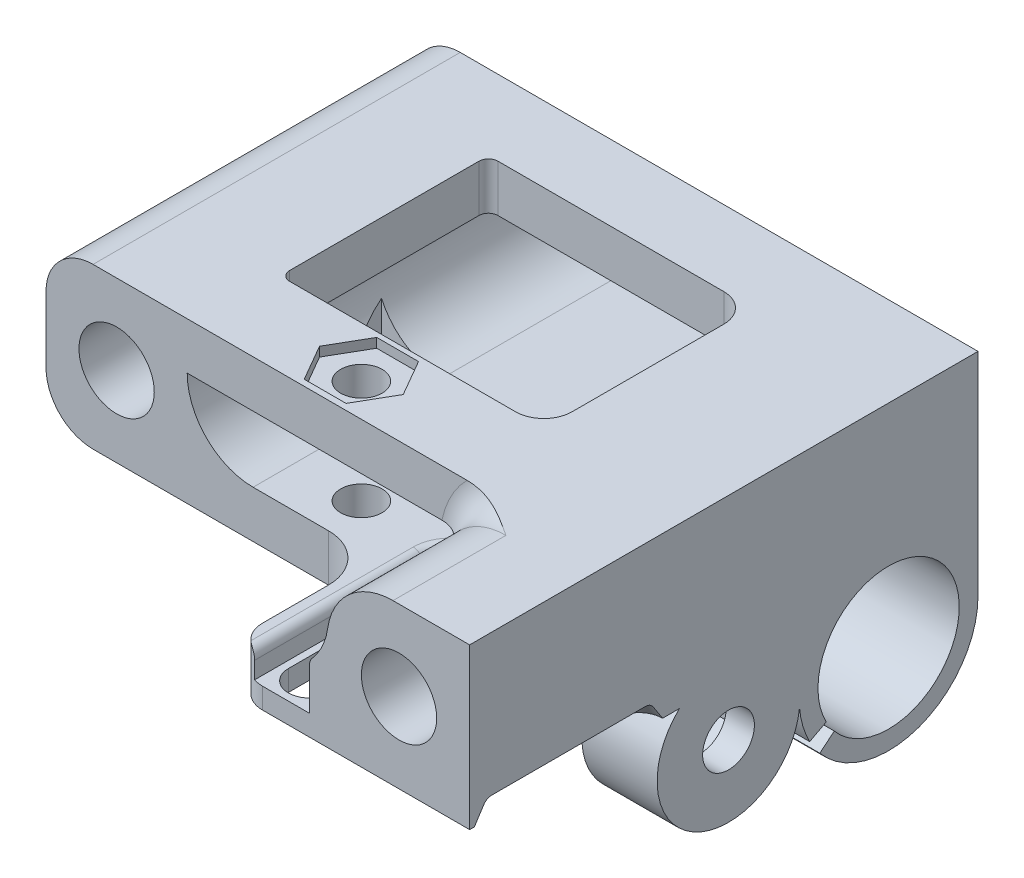
SolidWorks part; units mm, degrees
material "ABS generico"
ref_plane "Front Plane" through (0, 0, 0) normal (0, 0, 1) x (1, 0, 0)
ref_plane "Top Plane" through (0, 0, 0) normal (0, 1, 0) x (1, 0, 0)
ref_plane "Right Plane" through (0, 0, 0) normal (1, 0, 0) x (0, 0, -1)
sketch "Sketch1" plane through (0, 0, 0) normal (1, 0, 0) x (0, 0, -1)
  line L1 (21.1236, -26.9641) -> (22.8813, -26.0274)
  line L3 (23.7305, -27.2923) -> (22.1984, -28.5649)
  line L4 (20.0416, -23.294) -> (20.0416, -17)
  line L8 (39, 0) -> (0, 0)
  line L12 (0, -17) -> (0, 0)
  line L13 (0, -17) -> (20.0416, -17)
  line L15 (39, -22.5) -> (39, 0)
  line L19 (16.5, -29.4282) -> (20.0416, -23.294) construction
  line L20 (8.5, -29.4282) -> (16.5, -29.4282) construction
  line L21 (4.5, -22.5) -> (8.5, -29.4282) construction
  line L22 (4.5, -17) -> (4.5, -22.5) construction
  arc A0 (23.7305, -27.2923) -> (22.8813, -26.0274) centre (29.5041, -22.4988) ccw
  arc A1 (20.0416, -23.294) -> (21.1236, -26.9641) centre (29.5041, -22.4988) ccw
  arc A2 (22.1984, -28.5649) -> (39, -22.5) centre (29.5041, -22.4988) ccw
  circle A5 centre (12.5, -22.5) radius 2.75 construction
  dimension "D2" = 7.5042
  dimension "D3" = 9.4959
  dimension "D1" = 39
  dimension "D4" = 17
extrude "Extrude1" add sketch "Sketch1" against normal blind 60
sketch "Sketch2" plane through (0, 0, 0) normal (0, 0, 1) x (1, 0, 0)
  line L0 (-60, -8.5) -> (0, -8.5) construction
  line L1 (-60, 0) -> (-60, -17) construction
  line L2 (0, 0) -> (0, -17) construction
  line L3 (-30, 1.8171) -> (-30, -40.9837) construction
  line L5 (-15, -12) -> (-45, -12)
  line L6 (-15, -12) -> (-15, -5)
  line L7 (-15, -5) -> (-45, -5)
  line L8 (-45, -12) -> (-45, -5)
  line L9 (-15, -12) -> (-45, -5) construction
  line L10 (-15, -5) -> (-45, -12) construction
  circle A0 centre (-52.5, -8.5) radius 4
  circle A1 centre (-7.5, -8.5) radius 4
  point P12 (-30, -8.5)
  dimension "D1" = 8
  dimension "D2" = 22.5
  dimension "D3" = 7.5
  dimension "D4" = 7
  dimension "D5" = 30
extrude "Extrude2" cut sketch "Sketch2" against normal up to surface (39 mm away) up to face at (-30, -11.25, -39)
sketch "Sketch3" plane through (0, 0, 0) normal (0, 0, 1) x (1, 0, 0)
  line L0 (-52.5, -8.5) -> (-7.5, -8.5) construction
  line L1 (-52.5, -8.5) -> (-52.5, 8.8734) construction
  line L2 (-32.5, -8.5) -> (-32.5, 8.8734) construction
  dimension "D1" = 20
sketch "Sketch4" plane through (0, 0, 0) normal (1, 0, 0) x (0, 0, -1)
  line L0 (7.2804, -17) -> (20.0416, -17)
  line L1 (12.5, -17.9967) -> (8.6, -20.2483) construction
  line L2 (8.6, -20.2483) -> (8.6, -24.7517) construction
  line L3 (8.6, -24.7517) -> (12.5, -27.0033) construction
  line L4 (12.5, -27.0033) -> (16.4, -24.7517) construction
  line L5 (16.4, -24.7517) -> (16.4, -20.2483) construction
  line L6 (16.4, -20.2483) -> (12.5, -17.9967) construction
  line L7 (0, -17) -> (20.0416, -17) construction
  line L8 (20.0416, -17) -> (20.0817, -22.3872)
  circle A0 centre (12.5, -22.5) radius 3.9 construction
  arc A1 (7.2804, -17) -> (20.0817, -22.3872) centre (12.5, -22.5) ccw
  dimension "D1" = 7.8
extrude "Extrude3" add sketch "Sketch4" against normal blind 8
sketch "Sketch5" plane through (0, 0, 0) normal (1, 0, 0) x (0, 0, -1)
  circle A0 centre (12.5, -22.5) radius 2.75
  dimension "D1" = 5.5
extrude "Extrude4" cut sketch "Sketch5" against normal up to surface (8 mm away) up to face at (-8, -22.1484, -14.2839)
sketch "Sketch6" plane through (-8, 0, 0) normal (-1, 0, 0) x (0, 0, 1)
  line L1 (-12.5, -17.8812) -> (-16.5, -20.1906)
  line L2 (-16.5, -20.1906) -> (-16.5, -24.8094)
  line L3 (-16.5, -24.8094) -> (-12.5, -27.1188)
  line L4 (-12.5, -27.1188) -> (-8.5, -24.8094)
  line L5 (-8.5, -24.8094) -> (-8.5, -20.1906)
  line L6 (-8.5, -20.1906) -> (-12.5, -17.8812)
extrude "Extrude5" cut sketch "Sketch6" against normal blind 5
sketch "Sketch7" plane through (0, 0, 0) normal (0, 1, 0) x (1, 0, 0)
  line L2 (-31, -370.8295) -> (-31, 97.9462) construction
  line L6 (-30.9897, -180.6724) -> (-30.9897, -405.4164) construction
  circle A0 centre (-31, 4.5) radius 2.2
extrude "Extrude6" cut sketch "Sketch7" against normal up to surface (17 mm away) up to face at (-22.6667, -17, -9.1073)
sketch "Sketch8" plane through (0, 0, -39) normal (0, 0, -1) x (-1, 0, 0)
  line L0 (7.5, -8.5) -> (52.5, -8.5) construction
  line L1 (30, -8.5) -> (30, 3.0319) construction
  circle A0 centre (7.5, -8.5) radius 4.201
  circle A1 centre (52.5, -8.5) radius 1.25
  circle A2 centre (7.5, -8.5) radius 1.25
  circle A3 centre (52.5, -8.5) radius 4.201
  dimension "D1" = 2.5
extrude "Extrude7" add sketch "Sketch8" against normal blind 5
sketch "Sketch10" plane through (-60, 0, 0) normal (-1, 0, 0) x (0, 0, 1)
  line L1 (-20.0416, -17) -> (-39.247, -17)
  line L2 (-20.0416, -17) -> (-20.0416, -32.1139)
  line L3 (-20.0416, -32.1139) -> (-39.247, -32.1139)
  line L4 (-39.247, -17) -> (-39.247, -32.1139)
extrude "Extrude8" cut sketch "Sketch10" against normal blind 10
fillet "Fillet9" radius 10 2 edges at (-55, -17, -24.3976) (-55, -17, -34.6107)
fillet "Fillet11" radius 5 1 edges at (-60, 0, -19.5)
fillet "Fillet12" radius 5 5 edges at (-60, -17, -38.3198) (-60, -16.7094, -35.2462) (-60, -14.9946, -29.5041) (-60, -16.7094, -23.7621) (-60, -17, -10.6843)
sketch "Sketch12" plane through (0, 0, 0) normal (0, 0, 1) x (1, 0, 0)
  line L0 (-15, -12) -> (-15, 2.5343) construction
  line L1 (0, 0) -> (-20.7492, 0) construction
  line L2 (-55, 0) -> (0, 0) construction
  line L3 (-45, -12) -> (-15, -12) construction
  line L4 (-15, 0) -> (0, 0)
  line L5 (-11.5, -8.5) -> (-11.5, 2.5343) construction
  line L6 (-15, -17) -> (0, -17)
  line L7 (0, 0) -> (0, -17)
  line L8 (-15, -17) -> (-25, -17)
  line L9 (-25, -12) -> (-15, -12)
  line L10 (-15, -12) -> (-15, 0)
  line L11 (-25, -17) -> (-25, -12)
  circle A0 centre (-7.5, -8.5) radius 4
  point P21 (-14.5, -8.5)
  point P22 (-14.5, 2.5343)
  dimension "D3" = 8
  dimension "D1" = 10
extrude "Extrude10" add sketch "Sketch12" along normal blind 15
sketch "Sketch13" plane through (0, -17, 0) normal (0, -1, 0) x (1, 0, 0)
  line L2 (-20, -5.2455) -> (-20, 23.7024) construction
  line L4 (-25, 0) -> (-9.3359, 0) construction
  line L5 (-25, 15) -> (-25, 0) construction
  line L6 (-20, 12) -> (-20, -3) construction
  line L7 (-17.75, 12) -> (-17.75, -3)
  line L8 (-22.25, 12) -> (-22.25, -3)
  line L9 (-25, 15) -> (0, 15) construction
  arc A0 (-17.75, 12) -> (-22.25, 12) centre (-20, 12) ccw
  arc A1 (-22.25, -3) -> (-17.75, -3) centre (-20, -3) ccw
  point P14 (-20, 4.5)
  dimension "D2" = 3
  dimension "D1" = 5
extrude "Extrude11" cut sketch "Sketch13" against normal up to surface (5 mm away) up to face at (-28.8, -12, -4.5)
sketch "Sketch14" plane through (0, -17, 0) normal (0, -1, 0) x (1, 0, 0)
  line L0 (1.5, -3) -> (1.5, 12)
  line L1 (-12, -10.2024) -> (-12, 22.3262) construction
  line L2 (-1.5, 12) -> (-1.5, -3)
  line L3 (-10.5, -3) -> (-10.5, 12)
  line L4 (-13.5, 12) -> (-13.5, -3)
  arc A0 (-1.5, -3) -> (1.5, -3) centre (0, -3) ccw
  arc A1 (1.5, 12) -> (-1.5, 12) centre (0, 12) ccw
  arc A2 (-10.5, 12) -> (-13.5, 12) centre (-12, 12) ccw
  arc A3 (-13.5, -3) -> (-10.5, -3) centre (-12, -3) ccw
extrude "Extrude12" cut sketch "Sketch14" against normal blind 2
chamfer "Chamfer1" distance 1 angle 45 4 edges at (-13.5, -17, 4.5) (-12, -17, -4.5) (-12, -17, 13.5) (-10.5, -17, 4.5)
fillet "Fillet15" radius 3 1 edges at (-25, -14.5, 15)
sketch "Sketch15" plane through (0, 0, 0) normal (0, 1, 0) x (1, 0, 0)
  line L0 (-50, 22.8813) -> (0, 22.8813) construction
  line L1 (-41.4058, 31) -> (-18.5942, 31)
  arc A0 (-41.4058, 31) -> (-18.5942, 31) centre (-30, 22.8813) ccw
extrude "Extrude13" cut sketch "Sketch15" against normal blind 9
fillet "Fillet18" radius 1 4 edges at (-13.5, -15, 4.5) (-12, -15, 13.5) (-10.5, -15, 4.5) (-12, -15, -4.5)
fillet "Fillet19" radius 11 4 edges at (-13.5, -16, 4.5) (-12, -16, 13.5) (-10.5, -16, 4.5) (-12, -16, -4.5)
fillet "Fillet20" radius 7 1 edges at (-45, -12, -19.5)
sketch "Sketch16" plane through (0, -17, 0) normal (0, -1, 0) x (1, 0, 0)
  line L0 (-30, -8.881) -> (-30, -22.8813) construction
  line L1 (-44.4017, -20.0416) -> (-15.5983, -20.0416)
  arc A1 (-15.5983, -20.0416) -> (-44.4017, -20.0416) centre (-30, -22.8813) ccw
extrude "Extrude14" cut sketch "Sketch16" against normal up to surface (12 mm away) up to face at (-30, -5, -19.9405)
fillet "Fillet21" radius 7 1 edges at (-15, -12, -12)
fillet "Fillet22" radius 5 1 edges
sketch "Sketch17" plane through (0, 0, 0) normal (0, 1, 0) x (1, 0, 0)
  line L7 (-35.4444, 4.5) -> (-33.2222, 0.651)
  line L8 (-33.2222, 0.651) -> (-28.7778, 0.651)
  line L9 (-28.7778, 0.651) -> (-26.5556, 4.5)
  line L10 (-26.5556, 4.5) -> (-28.7778, 8.349)
  line L11 (-28.7778, 8.349) -> (-33.2222, 8.349)
  line L12 (-33.2222, 8.349) -> (-35.4444, 4.5)
  circle A0 centre (-31, 4.5) radius 3.849 construction
extrude "Cut-Extrude1" cut sketch "Sketch17" against normal blind 1
sketch "Sketch18" plane through (0, -5, 0) normal (0, -1, 0) x (1, 0, 0)
  line L0 (-20, -5.25) -> (-20, 17.0853) construction
  line L1 (-17, -3) -> (-17, 17.0853)
  line L2 (-23, -3) -> (-23, 17.0853)
  line L3 (-16.6454, -3) -> (-23.5438, -3) construction
  line L4 (-23, 17.0853) -> (-17, 17.0853)
  line L5 (-23, -5.25) -> (-23, 17.0853) construction
  line L6 (-17, -5.25) -> (-17, 17.0853) construction
  arc A0 (-22.25, -3) -> (-17.75, -3) centre (-20, -3) ccw construction
  arc A1 (-23, -3) -> (-17, -3) centre (-20, -3) ccw
  dimension "D1" = 3
  dimension "D2" = 3
extrude "Cut-Extrude2" cut sketch "Sketch18" along normal blind 9.8
fillet "Fillet33" radius 7 1 edges
fillet "Fillet34" radius 3 1 edges at (-12.3269, -1.3875, 0)
chamfer "Chamfer4" distance 1 angle 57 3 edges at (-1.0607, -17, 13.0607) (-1.0607, -17, -4.0607) (-1.5, -17, 4.5) first distance on face at (-22.4282, -17, -3.1966)
fillet "Fillet39" radius 1 3 edges at (-1.0607, -15, 13.0607) (-1.0607, -15, -4.0607) (-1.5, -15, 4.5)
fillet "Fillet40" radius 1 4 edges at (-17, -9.899, 6) (-18.1295, -10.8326, -5.3455) (-22.7386, -12, -4.2247) (-23, -12, 5.9142)
sketch "Schizzo1" plane through (0, -17, 0) normal (0, -1, 0) x (1, 0, 0)
  line L0 (-50, -20.0416) -> (-44.4017, -20.0416) construction
  line L1 (-46.1909, -20.0416) -> (-11.9276, -20.0416)
  line L2 (-46.1909, -20.0416) -> (-46.1909, -8.0389)
  line L3 (-46.1909, -8.0389) -> (-11.9276, -8.0389)
  line L4 (-11.9276, -20.0416) -> (-11.9276, -8.0389)
extrude "Estrusione-Estrusione1" add sketch "Schizzo1" against normal up to surface (5 mm away) up to face at (-30, -12, -29.5208)
sketch "Schizzo2" plane through (0, 0, 0) normal (0, 1, 0) x (1, 0, 0)
  line L0 (-44.0002, 31) -> (-15.9998, 31)
  line L2 (-15.9998, 8.881) -> (-15.9998, 31)
  line L3 (-44.0002, 8.881) -> (-44.0002, 31)
  line L4 (-30, 8.881) -> (-44.0002, 8.881)
  line L5 (-30, 8.881) -> (-15.9998, 8.881)
  arc A0 (-41.4058, 31) -> (-18.5942, 31) centre (-30, 22.8813) ccw construction
extrude "Taglio-Estrusione1" cut sketch "Schizzo2" against normal up to surface (5 mm away) up to face at (-24.6424, -5, -15.0643)
fillet "Raccordo1" radius 3 2 edges at (-15.9998, -2.5, -8.881) (-15.9998, -2.5, -31)
fillet "Raccordo2" radius 1 2 edges at (-44.0002, -2.5, -8.881) (-44.0002, -2.5, -31)
